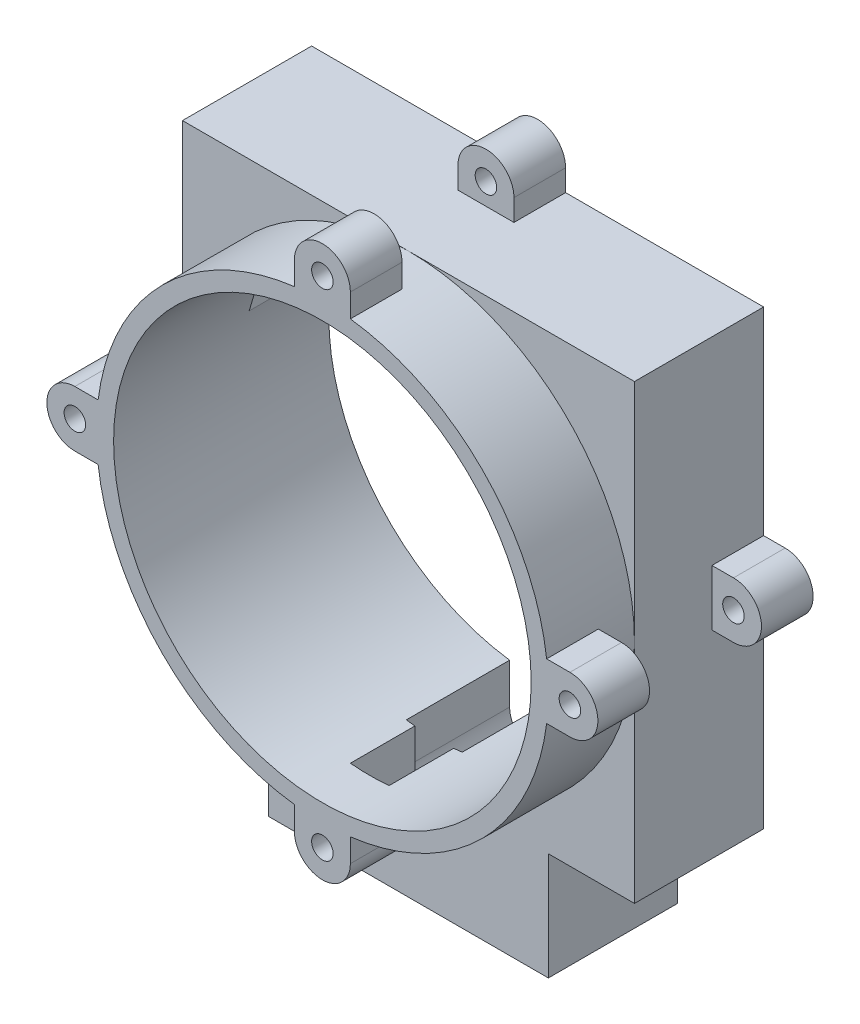
SolidWorks part; units mm, degrees
ref_plane "Front Plane" through (0, 0, 0) normal (0, 0, 1) x (1, 0, 0)
ref_plane "Top Plane" through (0, 0, 0) normal (0, 1, 0) x (1, 0, 0)
ref_plane "Right Plane" through (0, 0, 0) normal (1, 0, 0) x (0, 0, -1)
sketch "Sketch1" plane through (0, 0, 0) normal (0, 0, 1) x (1, 0, 0)
  line L0 (47, 47) -> (52.5, 52.5) construction
  line L1 (-52.5, 52.5) -> (52.5, 52.5)
  line L2 (-52.5, 52.5) -> (-52.5, -52.5)
  line L3 (-52.5, -52.5) -> (52.5, -52.5)
  line L4 (52.5, 52.5) -> (52.5, -52.5)
  line L5 (-32.5, -52.5) -> (32.5, -52.5)
  line L6 (-32.5, -52.5) -> (-32.5, -77.5)
  line L7 (-32.5, -77.5) -> (32.5, -77.5)
  line L8 (32.5, -52.5) -> (32.5, -77.5)
  line L9 (-47, 47) -> (47, 47)
  line L10 (-47, 47) -> (-47, -47)
  line L11 (-47, -47) -> (47, -47)
  line L12 (47, 47) -> (47, -47)
  line L13 (-52.5, -52.5) -> (-47, -47) construction
  line L14 (-47, 47) -> (-52.5, 52.5) construction
  point P6 (0, 52.5)
  point P7 (52.5, 0)
  dimension "D1" = 105
  dimension "D2" = 25
  dimension "D3" = 20
  dimension "D4" = 20
  dimension "D5" = 94
  dimension "D6" = 94
extrude "Boss-Extrude1" add sketch "Sketch1" along normal blind 20 contours L2 L1 L4 L3 | L10 L9 L12 L11 | L6 L5 L8 L7
sketch "Sketch2" plane through (0, 0, 20) normal (0, 0, 1) x (1, 0, 0)
  line L1 (-52.5, 52.5) -> (52.5, 52.5)
  line L2 (-52.5, 52.5) -> (-52.5, -52.5)
  line L3 (-52.5, -52.5) -> (52.5, -52.5)
  line L4 (52.5, 52.5) -> (52.5, -52.5)
  line L5 (-32.5, -52.5) -> (32.5, -52.5)
  line L6 (-32.5, -52.5) -> (-32.5, -77.5)
  line L7 (-32.5, -77.5) -> (32.5, -77.5)
  line L8 (32.5, -52.5) -> (32.5, -77.5)
  line M9 (-52.5, -52.5) -> (-32.5, -52.5)
  line M10 (-32.5, -52.5) -> (-32.5, -77.5)
  line M11 (-32.5, -77.5) -> (32.5, -77.5)
  line M12 (32.5, -77.5) -> (32.5, -52.5)
  line M13 (32.5, -52.5) -> (52.5, -52.5)
  line M14 (52.5, -52.5) -> (52.5, 52.5)
  line M15 (52.5, 52.5) -> (-52.5, 52.5)
  line M16 (-52.5, 52.5) -> (-52.5, -52.5)
  line M17 (47, -47) -> (-47, -47)
  line M18 (-47, -47) -> (-47, 47)
  line M19 (-47, 47) -> (47, 47)
  line M20 (47, 47) -> (47, -47)
extrude "Boss-Extrude2" add sketch "Sketch2" along normal blind 10 contours L3 M10 M11 M12 | L3 M9 M13 M14 M15 M16 M20 M17 M18 M19 | M17 M20 M19 M18 region at (0, 51.0151, 20) region at (0, -65, 20) region at (0, 0, 20)
sketch "Sketch3" plane through (0, 0, 0) normal (0, 0, -1) x (-1, 0, 0)
  line L0 (47, -47) -> (-47, -47) construction
  line L1 (-28.5, -47) -> (28.5, -47)
  line L2 (-28.5, -47) -> (-28.5, -73.5)
  line L3 (-28.5, -73.5) -> (28.5, -73.5)
  line L4 (28.5, -47) -> (28.5, -73.5)
  line L5 (-32.5, -52.5) -> (-32.5, -77.5) construction
  line L6 (32.5, -52.5) -> (32.5, -77.5) construction
  line L7 (32.5, -77.5) -> (-32.5, -77.5) construction
  dimension "D1" = 4
  dimension "D2" = 4
  dimension "D3" = 4
extrude "Cut-Extrude1" cut sketch "Sketch3" against normal up to surface (20 mm away) up to face at (0, 0, 20)
sketch "Sketch5" plane through (0, 0, 30) normal (0, 0, 1) x (1, 0, 0)
  circle A0 centre (0, 0) radius 52.5
  circle A1 centre (0, 0) radius 48.5
  dimension "D1" = 105
  dimension "D2" = 4
extrude "Boss-Extrude4" add sketch "Sketch5" along normal blind 20 contours A0
sketch "Sketch8" plane through (0, 0, 50) normal (0, 0, 1) x (1, 0, 0)
  circle A0 centre (0, 0) radius 48.5
  dimension "D1" = 97
extrude "Cut-Extrude3" cut sketch "Sketch8" against normal through all
sketch "Sketch9" plane through (0, 0, 50) normal (0, 0, 1) x (1, 0, 0)
  line L0 (57.5, 6.5) -> (48.5, 6.5)
  line L1 (48.5, 6.5) -> (48.5, -6.5)
  line L2 (48.5, -6.5) -> (57.5, -6.5)
  line L3 (-57.5, 6.5) -> (-48.5, 6.5)
  line L4 (-48.5, 6.5) -> (-48.5, -6.5)
  line L5 (-48.5, -6.5) -> (-57.5, -6.5)
  line L6 (-6.5, 57.5) -> (-6.5, 48.5)
  line L7 (6.5, 57.5) -> (6.5, 48.5)
  line L9 (6.5, 48.5) -> (-6.5, 48.5)
  line L11 (52.5, 0) -> (52.5, 52.5) construction
  line L12 (-52.5, 52.5) -> (-52.5, 0) construction
  line L13 (0, 52.5) -> (-52.5, 52.5) construction
  circle A0 centre (-57.5, 0) radius 2.5
  circle A1 centre (57.5, 0) radius 2.5
  arc A2 (-57.5, 6.5) -> (-57.5, -6.5) centre (-57.5, 0) ccw
  arc A3 (57.5, -6.5) -> (57.5, 6.5) centre (57.5, 0) ccw
  circle A5 centre (0, 57.5) radius 2.5
  arc A6 (6.5, 57.5) -> (-6.5, 57.5) centre (0, 57.5) ccw
  circle A7 centre (0, 0) radius 48.5 construction
  dimension "D1" = 5
  dimension "D2" = 5
  dimension "D3" = 4
  dimension "D4" = 4
  dimension "D5" = 4
  dimension "D6" = 5
  dimension "D7" = 5
  dimension "D9" = 5
  dimension "D8" = 5
extrude "Boss-Extrude5" add sketch "Sketch9" against normal up to surface (50 mm away) from offset 38 up to face at (0, -10.3929, 0) offset against normal yes
sketch "Sketch4" plane through (0, 0, 0) normal (0, 0, -1) x (-1, 0, 0)
  line L0 (32.5, -52.5) -> (32.5, -77.5) construction
  line L2 (-32.5, -64) -> (-32.5, -77.5)
  line L3 (44, -52.5) -> (44, -57.5) construction
  line L5 (-44, -57.5) -> (-44, -52.5)
  line L7 (44, -57.5) -> (44, -52.5)
  line L8 (-32.5, -77.5) -> (32.5, -77.5)
  line L9 (32.5, -64) -> (32.5, -77.5)
  line L10 (52.5, -52.5) -> (52.0213, -7.0735)
  line L11 (37.5, -64) -> (32.5, -64)
  line L12 (32.5, -77.5) -> (-32.5, -77.5) construction
  line L13 (37.5, -64) -> (32.5, -64) construction
  line L14 (-37.5, -64) -> (-32.5, -64)
  line L16 (-52.5, -52.5) -> (-52.5, 0)
  line L17 (52.5, -52.5) -> (44, -52.5)
  line L18 (-32.5, -52.5) -> (-52.5, -52.5) construction
  line L19 (-32.5, -52.5) -> (-32.5, -77.5) construction
  line L20 (-52.5, -52.5) -> (-44, -52.5)
  line L22 (-52.5, -52.5) -> (-52.5, 0) construction
  line L23 (-32.5, -52.5) -> (-52.5, -52.5) construction
  line L24 (52.5, -52.5) -> (32.5, -52.5) construction
  line L25 (-44, -28.64) -> (-44, -20.4022)
  line L26 (44, -28.64) -> (44, -20.4022)
  circle A0 centre (-37.5, -57.5) radius 2.5
  arc A1 (-44, -57.5) -> (-37.5, -64) centre (-37.5, -57.5) ccw
  circle A2 centre (37.5, -57.5) radius 2.5
  arc A4 (-47, -11.9687) -> (47, -11.9687) centre (0, 0) ccw construction
  arc A8 (44, -28.64) -> (52.0213, -7.0735) centre (0, 0) ccw
  arc A9 (37.5, -64) -> (44, -57.5) centre (37.5, -57.5) ccw
  arc A10 (-44, -20.4022) -> (44, -20.4022) centre (0, 0) ccw
  circle A11 centre (0, 0) radius 52.5 construction
  arc A12 (-52.5, 0) -> (-44, -28.64) centre (0, 0) ccw
  dimension "D1" = 4
  dimension "D2" = 6.5
  dimension "D3" = 5
  dimension "D4" = 5
  dimension "D5" = 5
  dimension "D6" = 5
extrude "Boss-Extrude6" add sketch "Sketch4" against normal blind 20
sketch "Sketch10" plane through (0, 0, 0) normal (0, 0, -1) x (-1, 0, 0)
  line L0 (-44, -47) -> (-28.5, -47)
  line L2 (-28.5, -47) -> (-28.5, -20.4022)
  line L3 (-28.5, -20.4022) -> (-44, -20.4022)
  line L4 (-44, -52.5) -> (-44, -57.5) construction
  line L5 (-44, -20.4022) -> (-44, -47)
  line L6 (45.5044, -20.4022) -> (30.0044, -20.4022)
  line L7 (30.0044, -20.4022) -> (30.0044, -47)
  line L8 (45.5044, -47) -> (45.5044, -20.4022)
  line L9 (30.0044, -47) -> (45.5044, -47)
  arc A0 (-44, -20.4022) -> (-28.5, -39.2428) centre (0, 0) ccw construction
  point P3 (0, 0)
  point P4 (45.5044, -47)
  dimension "D1" = 2
extrude "Cut-Extrude4" cut sketch "Sketch10" against normal up to surface (20 mm away) up to face at (45.5676, -21.1292, 20)
sketch "Sketch11" plane through (0, 0, 50) normal (0, 0, 1) x (1, 0, 0)
  circle A0 centre (-37.5, -57.5) radius 2.5
  circle A1 centre (37.5, -57.5) radius 2.5
  circle A2 centre (-37.5, -57.5) radius 2.5 construction
  circle A3 centre (37.5, -57.5) radius 2.5 construction
extrude "Boss-Extrude8" add sketch "Sketch11" against normal blind 15 from surface starting at face at (-40, -57.5, 20)
sketch "Sketch14" plane through (0, -47, 0) normal (0, 1, 0) x (1, 0, 0)
  line L0 (28.5, -20) -> (28.5, 0) construction
  line L1 (-30.0044, -20) -> (-47, -20)
  line L2 (-30.0044, -20) -> (-30.0044, 0)
  line L3 (-30.0044, 0) -> (-47, 0)
  line L4 (-47, -20) -> (-47, 0)
  line L5 (28.5, -20) -> (47, -20)
  line L6 (28.5, -20) -> (28.5, 0)
  line L7 (28.5, 0) -> (47, 0)
  line L8 (47, -20) -> (47, 0)
  line L9 (47, -20) -> (44, -20) construction
  line L10 (-30.0044, -20) -> (-30.0044, 0) construction
  line L11 (-30.0044, -20) -> (-45.5044, -20) construction
  point P12 (32.5842, -9.3003)
  point P19 (-26, -8.6715)
  point P22 (-47, 0)
  point P23 (-47, -10)
extrude "Boss-Extrude7" add sketch "Sketch14" along normal up to surface (35.0313 mm away) up to face at (-0.1856, 1.9741, 10)
sketch "Sketch16" plane through (0, 0, 20) normal (0, 0, 1) x (1, 0, 0)
  line L0 (-6.5, -57.4961) -> (-6.5, -52.0961)
  line L1 (6.5, -57.4961) -> (6.5, -52.0961)
  line L2 (32.5, -77.5) -> (-32.5, -77.5) construction
  circle A0 centre (0, -57.4961) radius 2.5
  arc A1 (-6.5, -57.4961) -> (6.5, -57.4961) centre (0, -57.4961) ccw
  circle A2 centre (0, 0) radius 52.5 construction
  arc A3 (-6.5, -52.0961) -> (6.5, -52.0961) centre (0, 0) ccw
  point P12 (0, 0)
  point P13 (0, 0)
  point P14 (-2.4335, -66.3877)
  point P15 (0, -77.5)
  dimension "D1" = 5
  dimension "D2" = 4
  dimension "D3" = 5.4
extrude "Boss-Extrude9" add sketch "Sketch16" along normal up to surface (30 mm away) up to face at (48.5, 0, 50)
sketch "Sketch17" plane through (0, 0, 20) normal (0, 0, 1) x (1, 0, 0)
  line L0 (32.5, -64) -> (32.5, -52.5)
  line L1 (32.5, -52.5) -> (44, -52.5)
  line L2 (32.5, -64) -> (37.5, -64)
  line L3 (44, -57.5) -> (44, -52.5)
  line L4 (-44, -52.5) -> (-32.5, -52.5)
  line L5 (-32.5, -52.5) -> (-32.5, -64)
  line L6 (-32.5, -64) -> (-37.5, -64)
  line L7 (-44, -57.5) -> (-44, -52.5)
  arc A0 (37.5, -64) -> (44, -57.5) centre (37.5, -57.5) ccw
  arc A1 (-37.5, -64) -> (-44, -57.5) centre (-37.5, -57.5) cw
extrude "Cut-Extrude5" cut sketch "Sketch17" against normal blind 8
sketch "Sketch18" plane through (0, 0, 50) normal (0, 0, 1) x (1, 0, 0)
  line L0 (-57.5, 6.5) -> (-52.0961, 6.5)
  line L3 (52.0961, 6.5) -> (57.5, 6.5)
  line L5 (57.5, -6.5) -> (52.0961, -6.5)
  line L9 (-57.5, -6.5) -> (-52.0961, -6.5)
  line L10 (-6.5, 57.5) -> (-6.5, 52.0961)
  line L11 (6.5, 57.5) -> (6.5, 52.0961)
  arc A1 (57.5, -6.5) -> (57.5, 6.5) centre (57.5, 0) ccw
  arc A3 (-57.5, 6.5) -> (-57.5, -6.5) centre (-57.5, 0) ccw
  arc A4 (-57.5, 6.5) -> (-57.5, -6.5) centre (-57.5, 0) ccw construction
  circle A5 centre (-57.5, 0) radius 2.5
  circle A6 centre (57.5, 0) radius 2.5
  circle A7 centre (57.5, 0) radius 2.5 construction
  circle A8 centre (-57.5, 0) radius 2.5 construction
  circle A9 centre (0, 57.5) radius 2.5
  circle A10 centre (0, 57.5) radius 2.5 construction
  arc A11 (6.5, 57.5) -> (-6.5, 57.5) centre (0, 57.5) ccw
  arc A12 (6.5, 57.5) -> (-6.5, 57.5) centre (0, 57.5) ccw construction
  arc A15 (-52.0961, 6.5) -> (-52.0961, -6.5) centre (0, 0) ccw
  arc A16 (6.5, -52.0961) -> (-6.5, -52.0961) centre (0, 0) ccw construction
  arc A17 (6.5, 52.0961) -> (-6.5, 52.0961) centre (0, 0) ccw
  arc A18 (52.0961, -6.5) -> (52.0961, 6.5) centre (0, 0) ccw
extrude "Boss-Extrude10" add sketch "Sketch18" against normal blind 12
sketch "Sketch19" plane through (0, 0, 0) normal (0, 0, -1) x (-1, 0, 0)
  line L0 (-6.5, -57.4961) -> (-6.5, -46.3829)
  line L1 (6.5, -57.4961) -> (6.5, -46.3829)
  arc A1 (-6.5, -57.4961) -> (6.5, -57.4961) centre (0, -57.4961) ccw
  arc A2 (-6.5, -57.4961) -> (6.5, -57.4961) centre (0, -57.4961) ccw construction
  arc A4 (-6.5, -46.3829) -> (6.5, -46.3829) centre (0, 0) ccw
  arc A5 (-47, 11.9687) -> (47, 11.9687) centre (0, 0) ccw construction
  point P3 (0, 0)
  point P9 (-6.5, -46.3829)
  point P10 (6.5, -46.8969)
  point P11 (0, 0)
  point P15 (0, 0)
extrude "Cut-Extrude12" cut sketch "Sketch19" against normal blind 24 and the other way blind 18
sketch "Sketch20" plane through (0, 0, 24) normal (0, 0, -1) x (-1, 0, 0)
  line L0 (4.5, -57.4961) -> (4.5, -48.2908)
  line L5 (-4.5, -57.4961) -> (-4.5, -48.2908)
  line L7 (-4.5, -50.2991) -> (-4.5, -57.4961)
  line L8 (4.5, -57.4961) -> (4.5, -50.2991)
  arc A9 (-6.5, -48.0625) -> (6.5, -48.0625) centre (0, 0) ccw construction
  arc A10 (-4.5, -50.2991) -> (4.5, -50.2991) centre (0, 0) ccw
  arc A11 (-4.5, -57.4961) -> (4.5, -57.4961) centre (0, -57.4961) ccw
  arc A13 (-4.5, -57.4961) -> (4.5, -57.4961) centre (0, -57.4961) ccw
  arc A14 (-4.5, -48.2908) -> (4.5, -48.2908) centre (0, 0) ccw
  point P9 (-2.4207, -42.6751)
  dimension "D1" = 2
extrude "Cut-Extrude13" cut sketch "Sketch20" against normal blind 15
